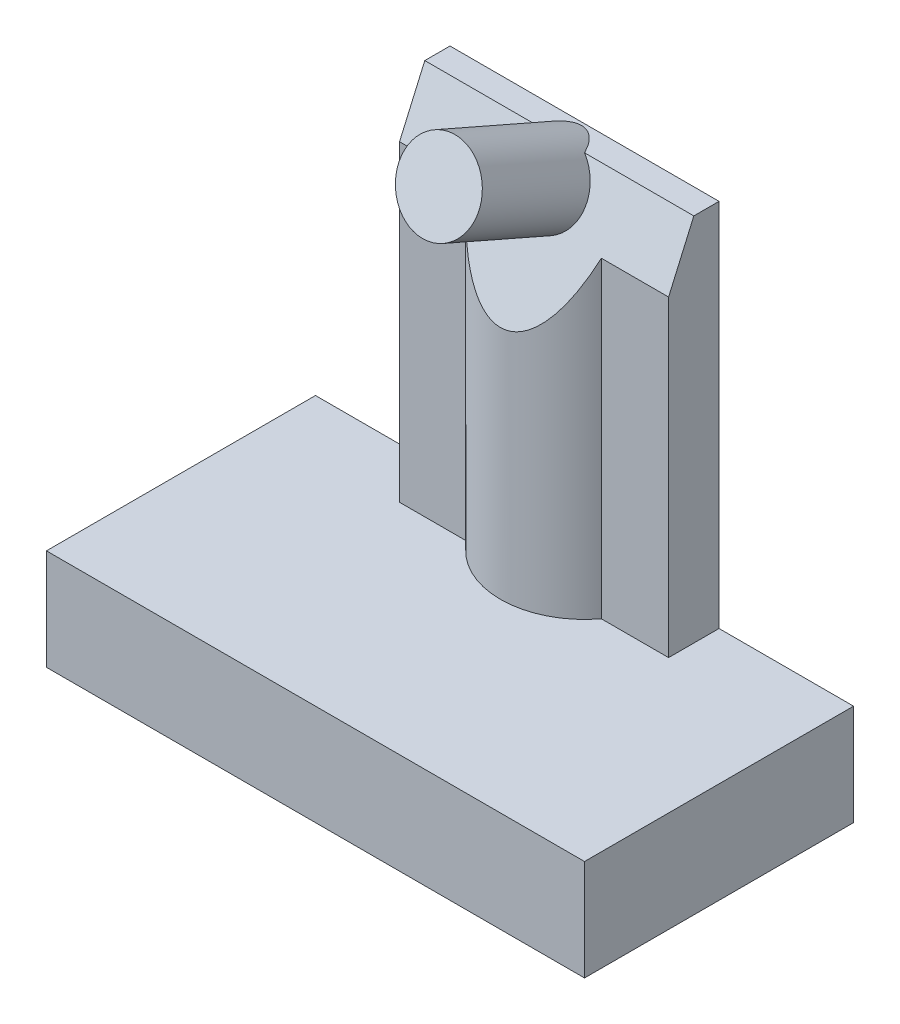
SolidWorks part; units mm, degrees
material "ABS"
ref_plane "Front Plane" through (0, 0, 0) normal (0, 0, 1) x (1, 0, 0)
ref_plane "Top Plane" through (0, 0, 0) normal (0, 1, 0) x (1, 0, 0)
ref_plane "Right Plane" through (0, 0, 0) normal (1, 0, 0) x (0, 0, -1)
sketch "Sketch1" plane through (0, 0, 0) normal (0, 1, 0) x (1, 0, 0)
  line L1 (8, -4) -> (-8, -4)
  line L2 (8, -4) -> (8, 4)
  line L3 (8, 4) -> (-8, 4)
  line L4 (-8, -4) -> (-8, 4)
  line L5 (8, -4) -> (-8, 4) construction
  line L6 (8, 4) -> (-8, -4) construction
  point P0 (0, 0)
  dimension "D1" = 16
  dimension "D2" = 8
extrude "Boss-Extrude1" add sketch "Sketch1" along normal blind 3
shell "Shell1" thickness 1 removed face at (0, 0, 0)
sketch "Sketch2" plane through (0, 2, 0) normal (0, -1, 0) x (1, 0, 0)
  circle A0 centre (0, 0) radius 1.5
  circle A1 centre (0, 0) radius 0.8
  dimension "D1" = 3
  dimension "D2" = 1.6
extrude "Boss-Extrude2" add sketch "Sketch2" along normal blind 2
sketch "Sketch3" plane through (0, 3, 0) normal (0, 1, 0) x (1, 0, 0)
  line L0 (0, 0) -> (0, 4) construction
  line L1 (8, 4) -> (-8, 4) construction
  line L2 (-4, 4) -> (4, 4)
  line L3 (4, 4) -> (4, 2.5)
  line L4 (4, 2.5) -> (2, 2.5)
  line L5 (-4, 2.5) -> (-2, 2.5)
  line L6 (-4, 4) -> (-4, 2.5)
  arc A0 (-2, 2.5) -> (2, 2.5) centre (0, 4) ccw
  dimension "D2" = 5
  dimension "D1" = 4
  dimension "D3" = 1.5
extrude "Boss-Extrude3" add sketch "Sketch3" along normal blind 11
sketch "Sketch4" plane through (4, 0, 0) normal (1, 0, 0) x (0, 0, -1)
  line L0 (3.25, 14) -> (1.5, 14)
  line L1 (2.5, 14) -> (4, 14) construction
  line L2 (1.5, 14) -> (1.5, 10)
  line L3 (1.5, 14) -> (1.5, 3) construction
  line L4 (1.5, 10) -> (3.25, 14)
  dimension "D1" = 4
extrude "Cut-Extrude1" cut sketch "Sketch4" against normal through all
sketch "Sketch5" plane through (0, 1.0557, 2.4131) normal (0, 0.4008, 0.9162) x (1, 0, 0)
  line L0 (-4, 13.1933) -> (4, 13.1933) construction
  line L1 (-4, 12.2577) -> (-4, 14.1289) construction
  line L2 (4, 12.2577) -> (4, 14.1289) construction
  line L3 (0, 14.4295) -> (0, 9.7628) construction
  line L4 (4, 14.4295) -> (-4, 14.4295) construction
  circle A0 centre (0, 13.1933) radius 1.2
  ellipse E0 centre (0, 16) end of major axis (0, 9.7628) minor radius 2.5 (-2, 12.2577) -> (2, 12.2577) ccw construction
  dimension "D1" = 2.4
extrude "Boss-Extrude4" add sketch "Sketch5" against normal up to next and the other way blind 3.5
